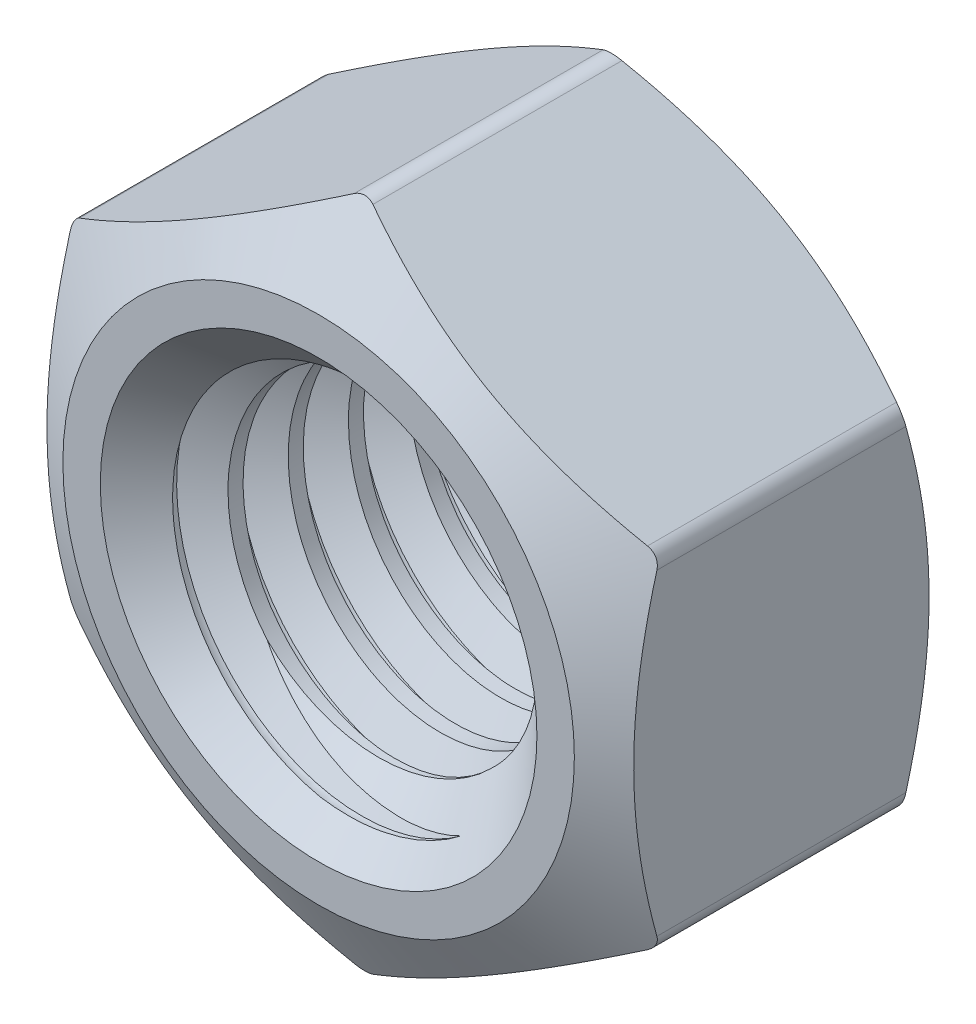
SolidWorks part; units mm, degrees
ref_plane "Front Plane" through (0, 0, 0) normal (0, 0, 1) x (1, 0, 0)
ref_plane "Top Plane" through (0, 0, 0) normal (0, 1, 0) x (1, 0, 0)
ref_plane "Right Plane" through (0, 0, 0) normal (1, 0, 0) x (0, 0, -1)
ref_plane "mirror_plane" through (0, 0, 2.25) normal (0, 0, 1) x (1, 0, 0)
sketch "Sketch1" plane through (0, 0, 0) normal (0, 0, 1) x (1, 0, 0)
  line L1 (0, 4.5) -> (-3.8971, 2.25)
  line L2 (-3.8971, 2.25) -> (-3.8971, -2.25)
  line L3 (-3.8971, -2.25) -> (0, -4.5)
  line L4 (0, -4.5) -> (3.8971, -2.25)
  line L5 (3.8971, -2.25) -> (3.8971, 2.25)
  line L6 (3.8971, 2.25) -> (0, 4.5)
  circle A0 centre (0, 0) radius 2.1
  circle A1 centre (0, 0) radius 3.8971 construction
  dimension "D1" = 4.2
  dimension "D2" = 9
extrude "Boss-Extrude1" add sketch "Sketch1" along normal blind 4.5
chamfer "Chamfer1" distance 0.8 angle 45 2 edges at (2.1, 0, 4.5) (2.1, 0, 0)
sketch "Sketch2" plane through (0, 0, 0) normal (0, 0, 1) x (1, 0, 0)
  circle A0 centre (0, 0) radius 2.1 construction
  circle A1 centre (0, 0) radius 2.1
curve "Helix/Spiral1" pitch 0.8 height 4.5 radius 2.1 centre (0, 0, 0) axis (0, 0, 1) start towards (0, 1, 0)
sketch "Sketch3" plane through (0, 0, 0) normal (1, 0, 0) x (0, 0, -1)
  line L0 (-0.1, 1.9268) -> (0.3, 2.6196) construction
  line L1 (0.3, 2.6196) -> (0.7, 1.9268) construction
  line L2 (0.7, 1.9268) -> (-0.1, 1.9268) construction
  line L3 (0, 2.1) -> (0.6, 2.1) construction
  line L4 (0.25, 2.533) -> (0.35, 2.533) construction
  line L5 (0.3, 2.6196) -> (0.3, 1.9268) construction
  line L6 (0.25, 2.533) -> (0, 2.1)
  line L7 (0, 2.1) -> (0, 1.9268)
  line L8 (0, 1.9268) -> (0.6, 1.9268)
  line L9 (0.6, 1.9268) -> (0.6, 2.1)
  line L10 (0.6, 2.1) -> (0.35, 2.533)
  arc A0 (0.25, 2.533) -> (0.35, 2.533) centre (0.3, 2.2732) cw
  dimension "D1" = 0.8
  dimension "D2" = 0.1732
  dimension "D3" = 0.0866
sweep "Cut-Sweep8" cut profiles "Sketch3" path "Helix/Spiral1" align with end faces yes
sketch "Sketch4" plane through (0, 0, 0) normal (0, 0, -1) x (-1, 0, 0)
  line L1 (0, 4.5) -> (3.8971, 2.25) construction
  circle A1 centre (0, 0) radius 3.3971
  dimension "D1" = 0.5
extrude "Cut-Extrude2" cut sketch "Sketch4" against normal blind 18 draft 60 flip side to cut
mirror "Mirror1" about plane through (0, 0, 2.25) normal (0, 0, 1) of "Cut-Extrude2"
fillet "Fillet1" radius 0.25 6 edges at (0, -4.5, 2.25) (-3.8971, -2.25, 2.25) (-3.8971, 2.25, 2.25) (3.8971, -2.25, 2.25) (3.8971, 2.25, 2.25) (0, 4.5, 2.25)
equation "\"size\"= 5"
equation "\"pitch\"= 0.8"
equation "\"tap_drill\"= \"size\" - \"pitch\""
equation "\"D1@Sketch1\"=\"tap_drill\""
equation "\"D2@Sketch1\"=\"size\"*1.8"
equation "\"D1@Boss-Extrude1\"=\"size\"*0.9"
equation "\"D3@Helix/Spiral1\"=\"size\"*0.9"
equation "\"D4@Helix/Spiral1\"=\"pitch\""
equation "\"D1@Chamfer1\"=\"pitch\""
equation "\"D1@Sketch3\"=\"pitch\""
equation "\"D2@Sketch3\"=\"pitch\"*sin(60)*0.25"
equation "\"D3@Sketch3\"=\"pitch\"*sin(60)*0.125"
equation "\"D1@mirror_plane\" = \"size\" * 0.45"
